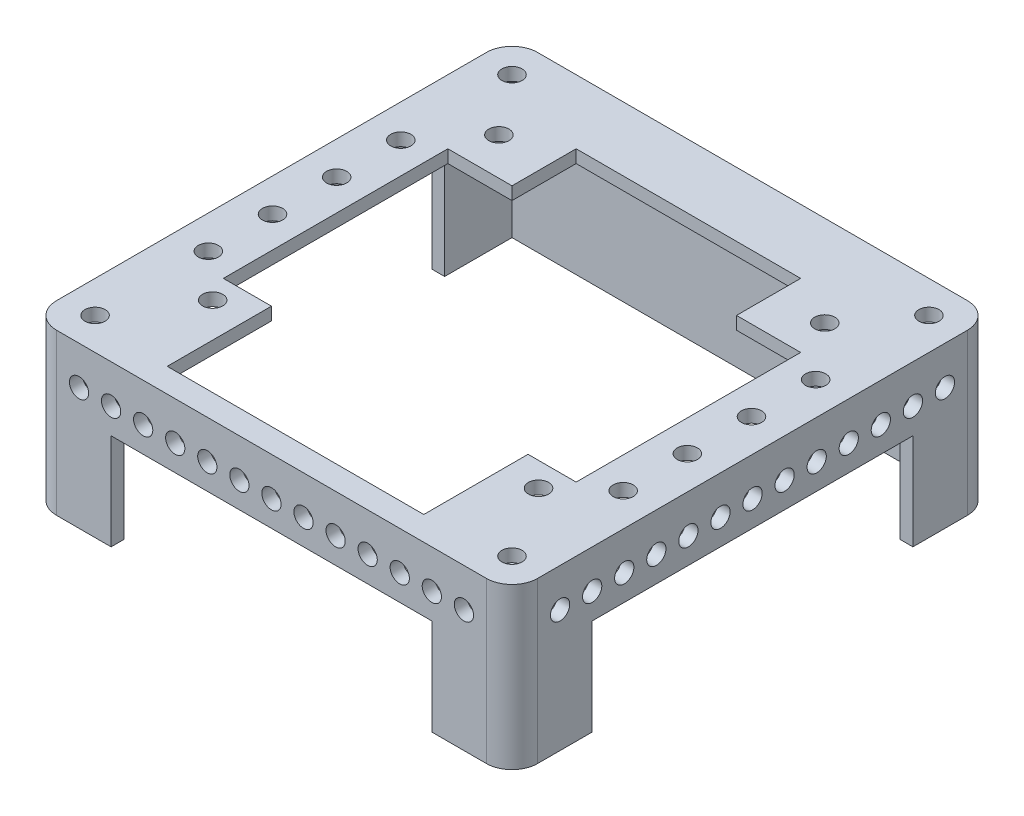
SolidWorks part; units mm, degrees
material "Custom Plastic"
ref_plane "Front Plane" through (0, 0, 0) normal (0, 0, 1) x (1, 0, 0)
ref_plane "Top Plane" through (0, 0, 0) normal (0, 1, 0) x (1, 0, 0)
ref_plane "Right Plane" through (0, 0, 0) normal (1, 0, 0) x (0, 0, -1)
sketch "Sketch1" plane through (0, 0, 0) normal (0, 1, 0) x (1, 0, 0)
  circle A2 centre (-50.8, 46.711) radius 3.15
  circle A3 centre (50.8, -42.532) radius 3.15
  circle A4 centre (-50.8, -42.532) radius 3.15
  circle A5 centre (50.8, 46.711) radius 3.15
sketch "Sketch9" plane through (0, 0, 0) normal (0, 1, 0) x (1, 0, 0)
  circle A0 centre (64.67, -30) radius 3.15
  circle A1 centre (-64.67, -30) radius 3.15
  circle A4 centre (64.67, -10) radius 3.15
  circle A5 centre (-64.67, -10) radius 3.15
  circle A6 centre (64.67, 10) radius 3.15
  circle A7 centre (-64.67, 10) radius 3.15
  circle A8 centre (64.67, 30) radius 3.15
  circle A9 centre (-64.67, 30) radius 3.15
  dimension "D1" = 4
extrude "Boss-Extrude10" add sketch "Sketch9" against normal mid plane 20 separate body
sketch "Sketch10" plane through (0, 0, 0) normal (0, 1, 0) x (1, 0, 0)
  line L0 (35, -55) -> (35, -35)
  line L1 (-55, 55) -> (55, 55) construction
  line L2 (-55, 55) -> (-55, -55) construction
  line L3 (-55, -55) -> (55, -55) construction
  line L4 (55, 55) -> (55, -55) construction
  line L5 (35, -35) -> (55, -35)
  line L6 (55, -35) -> (55, 35)
  line L7 (55, 35) -> (35, 35)
  line L8 (35, 35) -> (35, 55)
  line L9 (35, 55) -> (-35, 55)
  line L10 (-35, 55) -> (-35, 35)
  line L11 (-35, 35) -> (-55, 35)
  line L12 (-55, 35) -> (-55, -35)
  line L13 (-55, -35) -> (-35, -35)
  line L14 (-35, -35) -> (-35, -55)
  line L15 (35, -55) -> (-35, -55)
  point P0 (0, 0)
extrude "Boss-Extrude12" add sketch "Sketch10" against normal mid plane 20 separate body
sketch "Sketch15" plane through (0, 0, 0) normal (0, 1, 0) x (1, 0, 0)
  circle A2 centre (-50.8, 46.711) radius 3.15
  circle A3 centre (50.8, -42.532) radius 3.15
  circle A4 centre (-50.8, -42.532) radius 3.15
  circle A5 centre (50.8, 46.711) radius 3.15
extrude "Boss-Extrude17" add sketch "Sketch15" against normal mid plane 20 separate body
move or copy body "Body-Move/Copy4" bodies to move or copy 139 142 141 140 copy no translate (0, 1, 0)
sketch "Sketch22" plane through (0, 0, 0) normal (0, 1, 0) x (1, 0, 0)
  line L1 (-75, 75) -> (75, 75)
  line L2 (-75, 75) -> (-75, -75)
  line L3 (-75, -75) -> (75, -75)
  line L4 (75, 75) -> (75, -75)
  line L5 (-75, 75) -> (75, -75) construction
  line L6 (-75, -75) -> (75, 75) construction
  point P0 (0, 0)
extrude "Boss-Extrude19" add sketch "Sketch22" along normal blind 4 separate body
sketch "Sketch29" plane through (0, 4, 0) normal (0, 1, 0) x (1, 0, 0)
  line L1 (-75, 75) -> (75, 75)
  line L2 (-75, 75) -> (-75, -75)
  line L3 (-75, -75) -> (75, -75)
  line L4 (75, 75) -> (75, -75)
  line L5 (-75, 75) -> (75, -75) construction
  line L6 (-75, -75) -> (75, 75) construction
  line L7 (-71, 71) -> (71, 71)
  line L8 (-71, 71) -> (-71, -71)
  line L9 (-71, -71) -> (71, -71)
  line L10 (71, 71) -> (71, -71)
  line L11 (-71, 71) -> (71, -71) construction
  line L12 (-71, -71) -> (71, 71) construction
  point P0 (0, 0)
  point P5 (0, 0)
extrude "Boss-Extrude20" add sketch "Sketch29" against normal blind 50
fillet "Fillet12" radius 8 4 edges at (-75, -21, -75) (-75, -21, 75) (75, -21, 75) (75, -21, -75)
sketch "Sketch31" plane through (0, 4, 0) normal (0, 1, 0) x (1, 0, 0)
  line L5 (-71, 50) -> (-79, 50)
  line L6 (-71, 50) -> (-71, -50)
  line L11 (-71, -50) -> (-79, -50)
  line L12 (-79, 50) -> (-79, -50)
  line L13 (79, 50) -> (71, 50)
  line L14 (79, 50) -> (79, -50)
  line L15 (79, -50) -> (71, -50)
  line L16 (71, 50) -> (71, -50)
  line L17 (79, 50) -> (71, -50) construction
  line L18 (79, -50) -> (71, 50) construction
  line L19 (-71, 50) -> (-79, -50) construction
  line L20 (-71, -50) -> (-79, 50) construction
  line L29 (-67, -75) -> (67, -75) construction
  line L30 (-50, -71) -> (50, -71)
  line L31 (-50, -71) -> (-50, -79)
  line L32 (-50, -79) -> (50, -79)
  line L33 (50, -71) -> (50, -79)
  line L34 (-50, -71) -> (50, -79) construction
  line L35 (-50, -79) -> (50, -71) construction
  point P0 (-75, 0)
  point P11 (75, 0)
  point P21 (0, -75)
extrude "Boss-Extrude21" add sketch "Sketch31" against normal blind 100 from offset 20 separate body offset against normal yes
combine bodies "Combine4" operation type subtract main body 154 bodies to subtract 156 158 155
sketch "Sketch35" plane through (0, 0, 0) normal (0, 1, 0) x (1, 0, 0)
  circle A0 centre (65, -65) radius 3.15
  circle A1 centre (-65, 65) radius 3.15
  circle A2 centre (-65, -65) radius 3.15
  circle A3 centre (65, 65) radius 3.15
extrude "Boss-Extrude25" add sketch "Sketch35" against normal mid plane 20 separate body
sketch "Sketch38" plane through (0, 0, 0) normal (0, 1, 0) x (1, 0, 0)
  line L1 (40, -67.5) -> (-40, -67.5)
  line L2 (40, -67.5) -> (40, -31.9382)
  line L3 (40, -31.9382) -> (-40, -31.9382)
  line L4 (-40, -67.5) -> (-40, -31.9382)
  line L5 (40, -67.5) -> (-40, -31.9382) construction
  line L6 (40, -31.9382) -> (-40, -67.5) construction
  point P0 (0, -49.7191)
extrude "Boss-Extrude27" add sketch "Sketch38" along normal through all and the other way through all separate body
combine bodies "Combine12" operation type subtract main body 183 bodies to subtract 196 190 189 188 187
combine bodies "Combine13" operation type subtract main body 198 bodies to subtract 146 145 144 143 124 113 112
sketch "Sketch40" plane through (0, 0, 0) normal (0, 1, 0) x (1, 0, 0)
  line L0 (71, -71) -> (71, 71) construction
  line L1 (-71, -71) -> (71, -71) construction
  line L2 (71, -51) -> (51, -51)
  line L3 (71, -51) -> (71, -71)
  line L4 (71, -71) -> (51, -71)
  line L5 (51, -51) -> (51, -71)
  line L6 (71, 71) -> (-71, 71) construction
  line L7 (51, 71) -> (71, 71)
  line L8 (51, 71) -> (51, 51)
  line L9 (51, 51) -> (71, 51)
  line L10 (71, 71) -> (71, 51)
  line L11 (-71, 71) -> (-71, -71) construction
  line L12 (-71, 51) -> (-51, 51)
  line L13 (-71, 51) -> (-71, 71)
  line L14 (-71, 71) -> (-51, 71)
  line L15 (-51, 51) -> (-51, 71)
  line L17 (-71, -51) -> (-51, -51)
  line L18 (-71, -51) -> (-71, -71)
  line L19 (-71, -71) -> (-51, -71)
  line L20 (-51, -51) -> (-51, -71)
  point P24 (53.95, 49.861)
  point P25 (-51.72, 51.5276)
  point P26 (-48.1118, 51.0398)
  point P27 (-49.0883, -48.1774)
  point P28 (50.735, -49.4096)
  point P29 (53.8778, 52.8143)
sketch "Sketch36" plane through (0, 0, 0) normal (0, 1, 0) x (1, 0, 0)
  line L0 (-46.5147, -46.5147) -> (-63.4853, -63.4853) construction
  line L2 (-40.1508, -52.8787) -> (-57.1213, -69.8492)
  line L6 (-46.5147, 46.5147) -> (-63.4853, 63.4853) construction
  line L9 (-52.8787, -40.1508) -> (-69.8492, -57.1213)
  line L12 (-52.8787, 40.1508) -> (-69.8492, 57.1213)
  line L13 (-40.1508, 52.8787) -> (-57.1213, 69.8492)
  line L14 (46.5147, -46.5147) -> (63.4853, -63.4853) construction
  line L15 (52.8787, -40.1508) -> (69.8492, -57.1213)
  line L16 (40.1508, -52.8787) -> (57.1213, -69.8492)
  line L17 (46.5147, 46.5147) -> (63.4853, 63.4853) construction
  line L18 (40.1508, 52.8787) -> (57.1213, 69.8492)
  line L19 (52.8787, 40.1508) -> (69.8492, 57.1213)
  arc A13 (-52.8787, 40.1508) -> (-40.1508, 52.8787) centre (-46.5147, 46.5147) ccw
  arc A14 (-57.1213, 69.8492) -> (-69.8492, 57.1213) centre (-63.4853, 63.4853) ccw
  arc A15 (-40.1508, -52.8787) -> (-52.8787, -40.1508) centre (-46.5147, -46.5147) ccw
  arc A16 (-69.8492, -57.1213) -> (-57.1213, -69.8492) centre (-63.4853, -63.4853) ccw
  arc A17 (52.8787, -40.1508) -> (40.1508, -52.8787) centre (46.5147, -46.5147) ccw
  arc A18 (57.1213, -69.8492) -> (69.8492, -57.1213) centre (63.4853, -63.4853) ccw
  arc A19 (40.1508, 52.8787) -> (52.8787, 40.1508) centre (46.5147, 46.5147) ccw
  arc A20 (69.8492, 57.1213) -> (57.1213, 69.8492) centre (63.4853, 63.4853) ccw
  point P2 (-55, 55)
  point P3 (-55, -55)
  point P12 (55, -55)
  point P19 (55, 55)
extrude "Boss-Extrude28" add sketch "Sketch36" against normal blind 3 separate body
extrude "Boss-Extrude31" add sketch "Sketch40" against normal blind 4.5 separate body
combine bodies "Combine15" operation type add bodies to combine 206 207 208 209 199
combine bodies "Combine16" operation type subtract main body 210 bodies to subtract 203 202 201 200
combine bodies "Combine17" operation type subtract main body 211 bodies to subtract 217 216 215 214 213 212
ref_plane "Plane2" through (0, 0, -75) normal (0, 0, -1) x (-1, 0, 0)
fillet "Fillet14" radius 15 4 edges at (-51, -3.75, 51) (-51, -3.75, -51) (51, -3.75, -51) (51, -3.75, 51)
sketch "Sketch42" plane through (0, 0, 75) normal (0, 0, 1) x (1, 0, 0)
  circle A0 centre (60, -8) radius 3
  circle A1 centre (50, -8) radius 3
  circle A2 centre (40, -8) radius 3
  circle A3 centre (30, -8) radius 3
  circle A4 centre (20, -8) radius 3
  circle A5 centre (10, -8) radius 3
  circle A6 centre (0, -8) radius 3
  circle A7 centre (-10, -8) radius 3
  circle A8 centre (-20, -8) radius 3
  circle A9 centre (-30, -8) radius 3
  circle A10 centre (-40, -8) radius 3
  circle A11 centre (-50, -8) radius 3
  circle A12 centre (-60, -8) radius 3
  point P2 (0, 0)
  point P3 (0, 0)
  dimension "D1" = 13
extrude "Cut-Extrude1" cut sketch "Sketch42" against normal blind 10
sketch "Sketch45" plane through (-75, 0, 0) normal (-1, 0, 0) x (0, 0, 1)
  circle A0 centre (-60, -8) radius 3
  circle A1 centre (-50, -8) radius 3
  circle A2 centre (-40, -8) radius 3
  circle A3 centre (-30, -8) radius 3
  circle A4 centre (-20, -8) radius 3
  circle A5 centre (-10, -8) radius 3
  circle A6 centre (0, -8) radius 3
  circle A7 centre (10, -8) radius 3
  circle A8 centre (20, -8) radius 3
  circle A9 centre (30, -8) radius 3
  circle A10 centre (40, -8) radius 3
  circle A11 centre (50, -8) radius 3
  circle A12 centre (60, -8) radius 3
  dimension "D1" = 13
extrude "Cut-Extrude2" cut sketch "Sketch45" against normal through all
